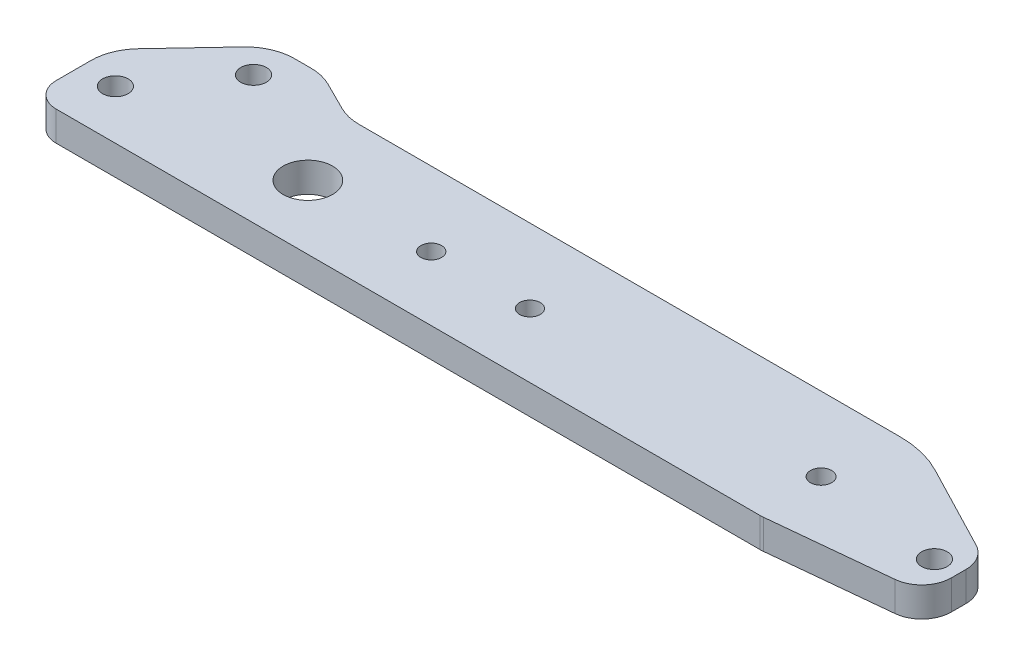
SolidWorks part; units mm, degrees
material "PE High Density"
ref_plane "Front Plane" through (0, 0, 0) normal (0, 0, 1) x (1, 0, 0)
ref_plane "Top Plane" through (0, 0, 0) normal (0, 1, 0) x (1, 0, 0)
ref_plane "Right Plane" through (0, 0, 0) normal (1, 0, 0) x (0, 0, -1)
sketch "Sketch1" plane through (0, 0, 0) normal (0, 1, 0) x (1, 0, 0)
  line L0 (159.9654, 15) -> (134.9654, 28)
  line L5 (159.9654, 3) -> (129.9654, 0)
  line L7 (-18, 16) -> (-18, 0)
  line L8 (-18, 0) -> (0, 0)
  line L9 (0, 0) -> (129.9654, 0)
  line L10 (159.9654, 3) -> (159.9654, 15)
  line L12 (-18, 16) -> (-2, 33)
  line L13 (-2, 33) -> (8, 33)
  line L14 (8, 33) -> (18, 28)
  line L15 (18, 28) -> (134.9654, 28)
  circle A0 centre (-11, 10) radius 2.6
  circle A1 centre (129, 13) radius 2.15
  circle A2 centre (25, 13) radius 5
  circle A3 centre (154.9654, 10) radius 2.6
  circle A4 centre (1, 26) radius 2.6
  circle A6 centre (50, 13) radius 2.1
  circle A7 centre (70, 13) radius 2.1
  dimension "D9" = 5.2
  dimension "D12" = 4.3
  dimension "D15" = 10
  dimension "D13" = 5.2
  dimension "D17" = 13
  dimension "D20" = 10
  dimension "D14" = 5.2
  dimension "D30" = 4.2
  dimension "D31" = 4.2
  dimension "D4" = 3
  dimension "D5" = 30
  dimension "D6" = 25
  dimension "D7" = 18
  dimension "D8" = 16
  dimension "D10" = 7
  dimension "D11" = 10
  dimension "D16" = 5
  dimension "D18" = 36
  dimension "D19" = 33
  dimension "D21" = 10
  dimension "D22" = 24
  dimension "D23" = 13
  dimension "D24" = 130
  dimension "D25" = 20
  dimension "D26" = 28
  dimension "D27" = 0
  dimension "D32" = 104
  dimension "D33" = 16
  dimension "D34" = 13
  dimension "D35" = 10
  dimension "D36" = 12
  dimension "D37" = 0
  dimension "D38" = 25
extrude "Boss-Extrude1" add sketch "Sketch1" along normal blind 6
fillet "Fillet1" radius 5 1 edges at (-18, 3, 0)
fillet "Fillet2" radius 6 3 edges at (129.9654, 3, 0) (159.9654, 3, -3) (159.9654, 3, -15)
fillet "Fillet3" radius 10 2 edges at (-2, 3, -33) (-18, 3, -16)
fillet "Fillet4" radius 20 1 edges at (134.9654, 3, -28)
fillet "Fillet5" radius 10 2 edges at (18, 3, -28) (8, 3, -33)
